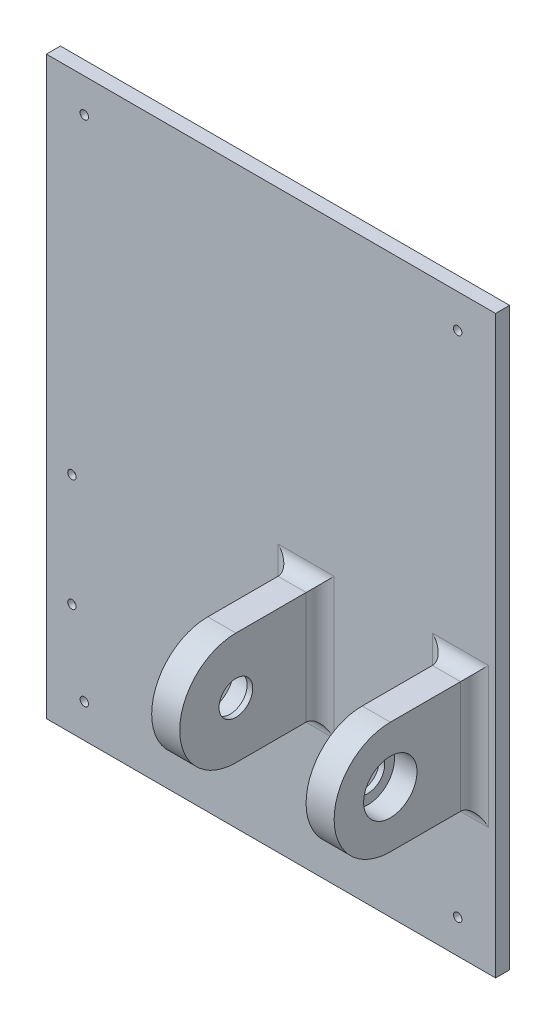
SolidWorks part; units mm, degrees
ref_plane "正面" through (0, 0, 0) normal (0, 0, 1) x (1, 0, 0)
ref_plane "平面" through (0, 0, 0) normal (0, 1, 0) x (1, 0, 0)
ref_plane "右側面" through (0, 0, 0) normal (1, 0, 0) x (0, 0, -1)
sketch "ｽｹｯﾁ2" plane through (0, 0, 0) normal (0, 0, 1) x (1, 0, 0)
  line L0 (-120, 124.8362) -> (-120, -80.1638)
  line L5 (-120, -80.1638) -> (40, -80.1638)
  line L6 (40, -80.1638) -> (40, 124.8362)
  line L7 (40, 124.8362) -> (-120, 124.8362)
  point P0 (0, 0)
  dimension "D1" = 205
  dimension "D2" = 120
  dimension "D3" = 40
extrude "ﾎﾞｽ - 押し出し1" add sketch "ｽｹｯﾁ2" along normal blind 5
sketch "ｽｹｯﾁ3" plane through (0, 0, 0) normal (0, 0, 1) x (1, 0, 0)
  line L0 (-32.5, 10) -> (-32.5, -30)
  line L1 (-32.5, -30) -> (-22.5, -30)
  line L2 (-22.5, -30) -> (-22.5, 10)
  line L3 (-22.5, 10) -> (-32.5, 10)
  dimension "D1" = 10
  dimension "D2" = 40
  dimension "D3" = 30
  dimension "D4" = 22.5
extrude "ﾎﾞｽ - 押し出し2" add sketch "ｽｹｯﾁ3" along normal blind 35
ref_plane "平面1" through (-32.5, 0, 0) normal (-1, 0, 0) x (0, 0, 1)
sketch "ｽｹｯﾁ4" plane through (-32.5, 0, 0) normal (-1, 0, 0) x (0, 0, 1)
  line L0 (35, 10) -> (35, -30) construction
  circle A0 centre (35, -10) radius 20
extrude "ﾎﾞｽ - 押し出し3" add sketch "ｽｹｯﾁ4" against normal blind 10
sketch "ｽｹｯﾁ5" plane through (-32.5, 0, 0) normal (-1, 0, 0) x (0, 0, 1)
  circle A0 centre (35, -10) radius 9.5
  dimension "D1" = 19
extrude "ｶｯﾄ - 押し出し1" cut sketch "ｽｹｯﾁ5" against normal blind 8
sketch "ｽｹｯﾁ13" plane through (-22.5, 0, 0) normal (1, 0, 0) x (0, 0, -1)
  circle A0 centre (-35, -10) radius 6
  dimension "D1" = 12
extrude "ｶｯﾄ - 押し出し2" cut sketch "ｽｹｯﾁ13" against normal through all
fillet "ﾌｨﾚｯﾄ1" radius 5 4 edges at (-27.5, -30, 5) (-32.5, -10, 5) (-27.5, 10, 5) (-22.5, -10, 5)
mirror "ﾐﾗｰ2" about plane through (0, 0, 0) normal (1, 0, 0) of "ﾌｨﾚｯﾄ1", "ｶｯﾄ - 押し出し2", "ｶｯﾄ - 押し出し1", "ﾎﾞｽ - 押し出し3", "ﾎﾞｽ - 押し出し2"
ref_plane "平面2" through (-22.5, 0, 0) normal (1, 0, 0) x (0, 0, -1)
sketch "ｽｹｯﾁ14" plane through (0, 0, 0) normal (0, 0, 1) x (1, 0, 0)
  circle A0 centre (-110.9, -0.35) radius 1.5
  circle A1 centre (-110.9, -40.35) radius 1.5
  dimension "D1" = 3
  dimension "D2" = 3
  dimension "D3" = 110.9
  dimension "D5" = 110.9
  dimension "D4" = 40
  dimension "D6" = 0.35
extrude "ｶｯﾄ - 押し出し3" cut sketch "ｽｹｯﾁ14" along normal blind 10
sketch "ｽｹｯﾁ15" plane through (0, 0, 0) normal (0, 0, 1) x (1, 0, 0)
  line L0 (-110.9, -0.35) -> (-110.9, -40.35) construction
  line L2 (-113.75, -1.9954) -> (-110.9, -3.6409)
  line L3 (-110.9, -3.6409) -> (-108.05, -1.9954)
  line L4 (-108.05, -1.9954) -> (-108.05, 1.2954)
  line L5 (-108.05, 1.2954) -> (-110.9, 2.9409)
  line L6 (-110.9, 2.9409) -> (-113.75, 1.2954)
  line L7 (-113.75, 1.2954) -> (-113.75, -1.9954)
  line L8 (-113.75, -41.9954) -> (-110.9, -43.6409)
  line L9 (-110.9, -43.6409) -> (-108.05, -41.9954)
  line L10 (-108.05, -41.9954) -> (-108.05, -38.7046)
  line L11 (-108.05, -38.7046) -> (-110.9, -37.0591)
  line L12 (-110.9, -37.0591) -> (-113.75, -38.7046)
  line L13 (-113.75, -38.7046) -> (-113.75, -41.9954)
  circle A0 centre (-110.9, -0.35) radius 3.381
  circle A1 centre (-110.9, -40.35) radius 2.85
  circle A2 centre (-110.9, -0.35) radius 2.85 construction
  circle A3 centre (-110.9, -40.35) radius 2.85 construction
  dimension "D1" = 5.7
  dimension "D2" = 5.7
  dimension "D3" = 5.7
extrude "ｶｯﾄ - 押し出し4" cut sketch "ｽｹｯﾁ15" along normal blind 3 contours A1 | L2 L3 L4 L5 L6 L7 | L8 L9 L10 L11 L12 L13
sketch "ｽｹｯﾁ16" plane through (0, 0, 5) normal (0, 0, 1) x (1, 0, 0)
  line L0 (-120, -80.1638) -> (-120, -50.1638)
  line L1 (-120, 124.8362) -> (-120, -80.1638) construction
  line L2 (-120, -50.1638) -> (40, -50.1638)
  line L3 (40, -80.1638) -> (40, 124.8362) construction
  line L4 (40, -50.1638) -> (40, -80.1638)
  line L5 (40, -80.1638) -> (-120, -80.1638)
  dimension "D1" = 30
sketch "ｽｹｯﾁ17" plane through (0, 0, 5) normal (0, 0, 1) x (1, 0, 0)
  line L0 (-106.5, 112.8362) -> (-106.5, -68.1638)
  line L1 (-106.5, -68.1638) -> (26.5, -68.1638)
  line L2 (26.5, -68.1638) -> (26.5, 112.8362)
  line L3 (26.5, 112.8362) -> (-106.5, 112.8362)
  line L4 (40, 124.8362) -> (-120, 124.8362) construction
  line L5 (-120, 124.8362) -> (-120, -80.1638) construction
  dimension "D1" = 133
  dimension "D2" = 181
  dimension "D3" = 12
  dimension "D4" = 13.5
sketch "ｽｹｯﾁ18" plane through (0, 0, 5) normal (0, 0, 1) x (1, 0, 0)
  circle A0 centre (-106.5, 112.8362) radius 1.5
  circle A1 centre (-106.5, -68.1638) radius 1.5
  circle A2 centre (26.5, -68.1638) radius 1.5
  circle A3 centre (26.5, 112.8362) radius 1.5
  dimension "D1" = 3
  dimension "D2" = 3
  dimension "D3" = 3
  dimension "D4" = 3
extrude "ｶｯﾄ - 押し出し5" cut sketch "ｽｹｯﾁ18" against normal through all both contours A1 | A2 | A0 | A3
equation "\"D5@ｽｹｯﾁ14\"=\"D3@ｽｹｯﾁ14\""
